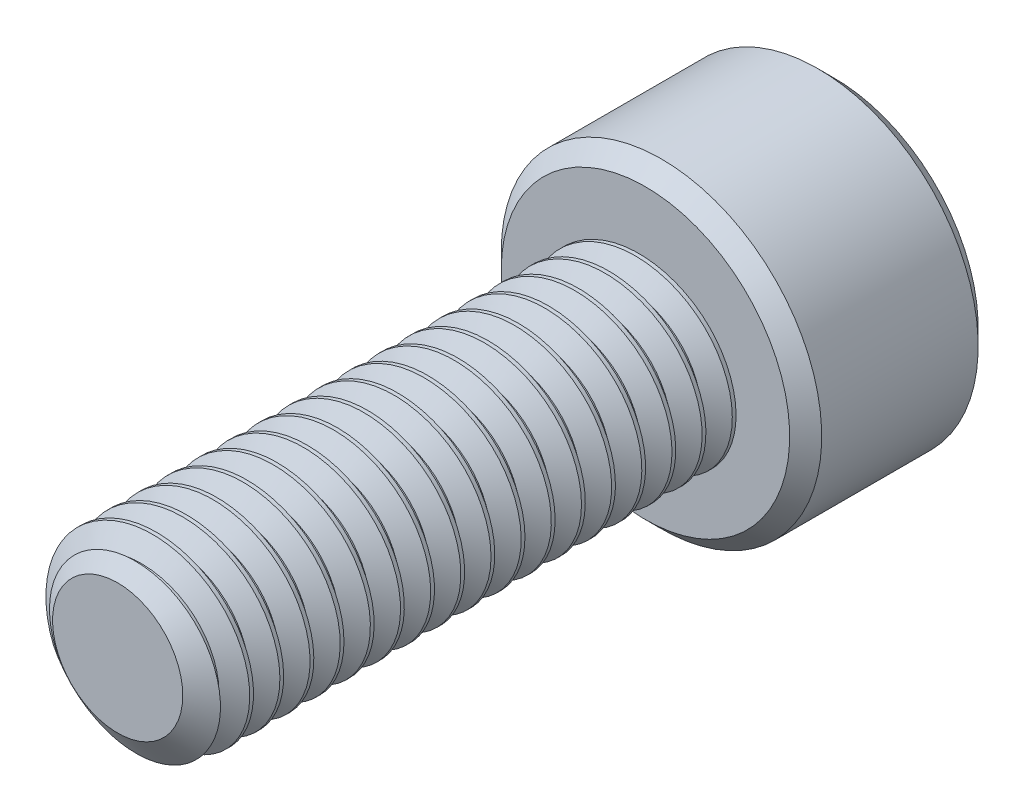
SolidWorks part; units mm, degrees
note: '?' marks a value the reader was unsure of.
ref_plane "xy_plane" through (0, 0, 0) normal (0, 0, 1) x (1, 0, 0)
ref_plane "zx_plane" through (0, 0, 0) normal (0, 1, 0) x (1, 0, 0)
ref_plane "yz_plane" through (0, 0, 0) normal (1, 0, 0) x (0, 0, -1)
ref_axis "x_axis" through (-4.675, 0, 0) along (1, 0, 0)?
ref_axis "y_axis" through (0, -4.675, 0) along (0, 1, 0)?
ref_axis "z_axis" through (0, 0, -14.84) along (0, 0, 1)?
sketch "Sketch1" plane through (0, 0, 0) normal (0, 0, 1) x (1, 0, 0)
  circle A0 centre (0, 0) radius 2.5
  dimension "OD" = 5
extrude "Extrude1" add sketch "Sketch1" against normal blind 14
sketch "Sketch2" plane through (0, 0, 0) normal (0, 0, 1) x (1, 0, 0)
  circle A0 centre (0, 0) radius 2.5 construction
  circle A1 centre (0, 0) radius 2.5
curve "Helix/Spiral1" pitch 0.8 height 14.8 turns 18.5 parameters "pitch"=0.8
sketch "Sketch3" plane through (0, 0, 0) normal (1, 0, 0) x (0, 0, -1)
  line L0 (-0.7, 2.5) -> (-0.4, 1.9804)
  line L1 (-0.4, 1.9804) -> (-0.3, 1.9804)
  line L2 (-0.3, 1.9804) -> (0, 2.5)
  line L3 (-0.7, 2.5) -> (0, 2.5)
  line L4 (-0.35, 2.5) -> (-0.35, 1.9804) construction
  line L5 (-0.55, 2.2402) -> (-0.15, 2.2402) construction
  line L6 (0, 2.5) -> (0, -2.5) construction
  dimension "D1" = 0.1
  dimension "D2" = 0.4
  dimension "D3" = 60
sweep "Cut-Sweep1" cut profiles "Sketch3" path "Helix/Spiral1"
sketch "Sketch4" plane through (0, 0, 0) normal (1, 0, 0) x (0, 0, -1)
  line L0 (0.5417, 2.5) -> (0, 1.7264)
  line L1 (0, 1.7264) -> (0, 2.5)
  line L2 (0.5417, 2.5) -> (0, 2.5)
  line L3 (-0.7, 2.5) -> (0, 2.5) construction
  line L4 (0, 0) -> (7.0209, 0) construction
  dimension "D1" = 55
  dimension "D2" = 0.254
revolve "Cut-Revolve1" cut sketch "Sketch4" angle 360 about L4
sketch "Sketch6" plane through (0, 0, -14) normal (0, 0, -1) x (-1, 0, 0)
  circle A0 centre (0, 0) radius 4.25
  dimension "head dia" = 8.5
extrude "Extrude2" add sketch "Sketch6" along normal blind 5
sketch "Sketch7" plane through (0, 0, -19) normal (0, 0, -1) x (-1, 0, 0)
  line L1 (0, 2.3094) -> (-2, 1.1547)
  line L2 (-2, 1.1547) -> (-2, -1.1547)
  line L3 (-2, -1.1547) -> (0, -2.3094)
  line L4 (0, -2.3094) -> (2, -1.1547)
  line L5 (2, -1.1547) -> (2, 1.1547)
  line L6 (2, 1.1547) -> (0, 2.3094)
  circle A0 centre (0, 0) radius 2 construction
  dimension "hex dia" = 4
extrude "Cut-Extrude1" cut sketch "Sketch7" against normal blind 3
sketch "Sketch8" plane through (0, 0, -19) normal (0, 0, -1) x (-1, 0, 0)
  circle A0 centre (0, 0) radius 2.3094
extrude "Cut-Extrude2" cut sketch "Sketch8" against normal through all draft 45
chamfer "Chamfer1" distance 0.425 angle 45 2 edges at (-4.25, 0, -19) (-4.25, 0, -14)
sketch "Sketch10" plane through (0, 0, -14) normal (0, 0, 1) x (1, 0, 0)
  circle A1 centre (0, 0) radius 2.5
  circle A2 centre (0, 0) radius 2.5
  dimension "D1" = 0
ref_plane "Plane1" through (0, 0, 0) normal (0, 0, 1) x (1, 0, 0)
extrude "partial thread" [suppressed] add sketch "Sketch10" along normal up to surface (13 mm away) separate body
chamfer "Chamfer2" [suppressed] distance 0.1 angle 45
combine bodies "Combine1" [suppressed] operation type add bodies to combine 107 108
sketch "Sketch9" plane through (0, 0, 0) normal (1, 0, 0) x (0, 0, -1)
  line L0 (0, 2.5) -> (0, -2.5) construction
  line L1 (2, 2.5) -> (2, -2.5) construction
  dimension "D1" = 2
equation "\"D3@Helix/Spiral1\" = \"screw length@Extrude1\"+\"pitch@Helix/Spiral1\""
equation "\"D1@Sketch3\" = \"pitch@Helix/Spiral1\"*.125"
equation "\"D2@Sketch3\" = \"pitch@Helix/Spiral1\"*.5"
equation "\"D1@Cut-Extrude1\" = \"hex dia@Sketch7\"*.75"
equation "\"D1@Chamfer1\" = \"head dia@Sketch6\"*.05"
equation "\"D1@Sketch9\" = \"pitch@Helix/Spiral1\"*2.5"
equation "\"D1@Chamfer2\"=\"OD@Sketch1\"*.02"
equation "\"screw length@Extrude1\"= \"externalParameters.this.length\""
